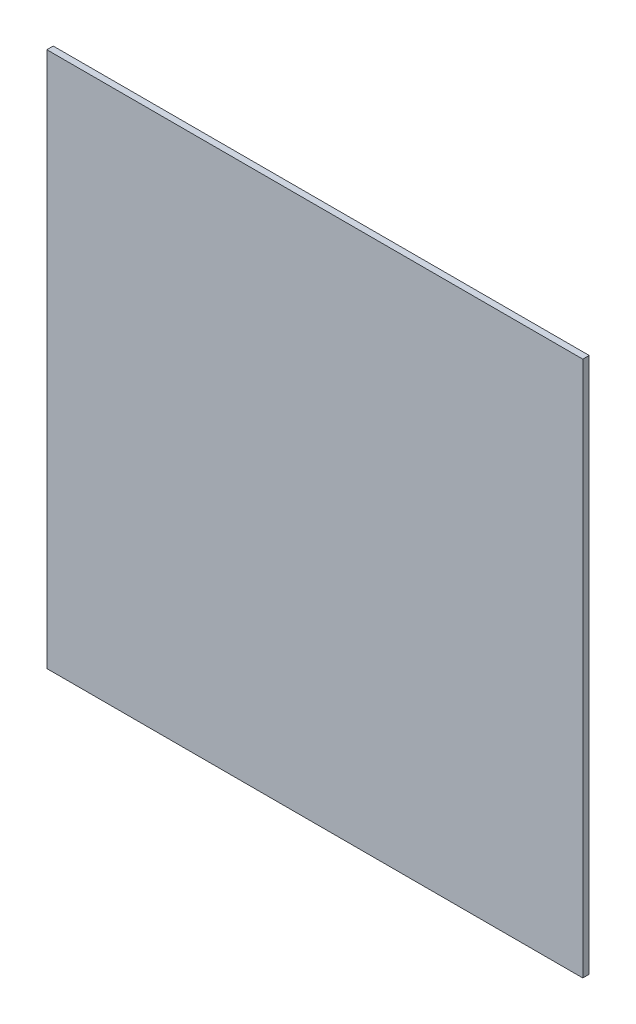
SolidWorks part; units mm, degrees
material "5052-O"
ref_plane "Front Plane" through (0, 0, 0) normal (0, 0, 1) x (1, 0, 0)
ref_plane "Top Plane" through (0, 0, 0) normal (0, 1, 0) x (1, 0, 0)
ref_plane "Right Plane" through (0, 0, 0) normal (1, 0, 0) x (0, 0, -1)
sketch "Sketch2" plane through (0, 0, 0) normal (0, 0, 1) x (1, 0, 0)
  line L1 (-167.7, 167.7) -> (167.7, 167.7)
  line L2 (-167.7, 167.7) -> (-167.7, -167.7)
  line L3 (-167.7, -167.7) -> (167.7, -167.7)
  line L4 (167.7, 167.7) -> (167.7, -167.7)
  dimension "D1" = 335.4
  dimension "D2" = 335.4
  dimension "D3" = 167.7
  dimension "D4" = 167.7
extrude "Boss-Extrude2" add sketch "Sketch2" along normal blind 4
